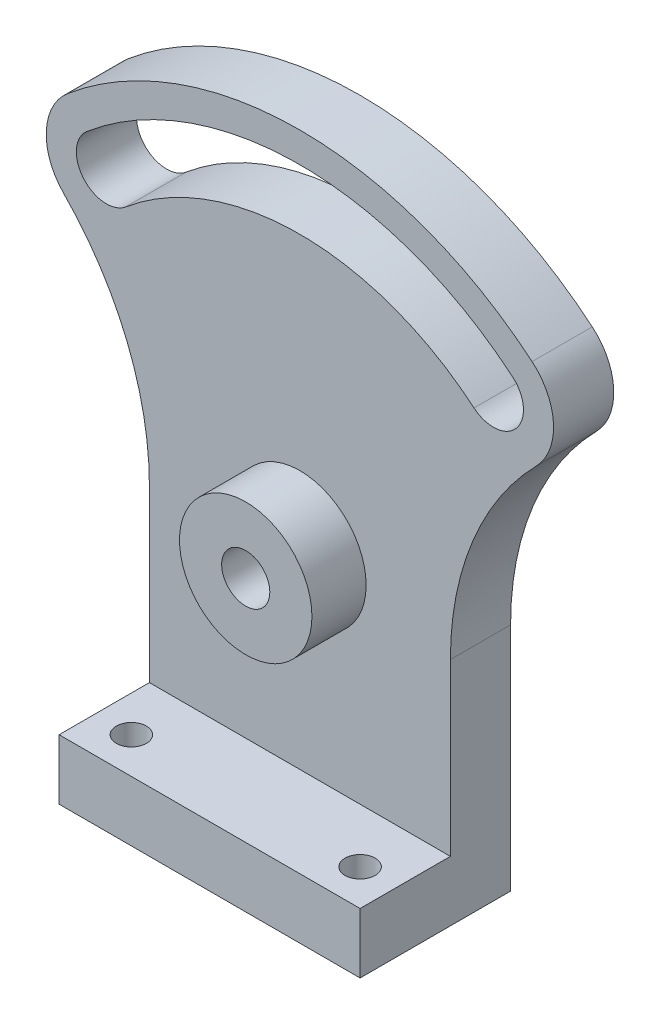
SolidWorks part; units mm, degrees
ref_plane "Front Plane" through (0, 0, 0) normal (0, 0, 1) x (1, 0, 0)
ref_plane "Top Plane" through (0, 0, 0) normal (0, 1, 0) x (1, 0, 0)
ref_plane "Right Plane" through (0, 0, 0) normal (1, 0, 0) x (0, 0, -1)
sketch "Sketch1" plane through (0, 0, 0) normal (0, 0, 1) x (1, 0, 0)
  line L0 (0, 0) -> (0, 23941.5913) construction
  line L1 (0, 0) -> (23941.5913, 0) construction
  line L2 (-25, -11) -> (25, -11)
  line L3 (-25, -21) -> (25, -21)
  line L4 (-25, -21) -> (-25, 17.3145)
  line L6 (25, -21) -> (25, 17.3145)
  circle A0 centre (0, 21) radius 4
  circle A1 centre (0, 21) radius 11
  arc A2 (-32.1394, 59.3022) -> (32.1394, 59.3022) centre (0, 21) cw construction
  arc A3 (38.5673, 66.9627) -> (-38.5673, 66.9627) centre (0, 21) ccw
  arc A4 (25.7115, 51.6418) -> (-25.7115, 51.6418) centre (0, 21) ccw
  arc A5 (25.7115, 51.6418) -> (38.5673, 66.9627) centre (32.1394, 59.3022) ccw
  arc A6 (-38.5673, 66.9627) -> (-25.7115, 51.6418) centre (-32.1394, 59.3022) ccw
  arc A7 (-32.1394, 59.3022) -> (32.1394, 59.3022) centre (0, 21) cw construction
  arc A8 (35.3533, 63.1324) -> (-35.3533, 63.1324) centre (0, 21) ccw
  arc A9 (28.9254, 55.472) -> (-28.9254, 55.472) centre (0, 21) ccw
  arc A10 (28.9254, 55.472) -> (35.3533, 63.1324) centre (32.1394, 59.3022) ccw
  arc A11 (-35.3533, 63.1324) -> (-28.9254, 55.472) centre (-32.1394, 59.3022) ccw
  arc A12 (25, 17.3145) -> (39.2828, 52.3043) centre (75, 17.3145) cw
  arc A13 (-25, 17.3145) -> (-39.2828, 52.3043) centre (-75, 17.3145) ccw
  point P5 (0, 0)
  point P17 (0, 71)
  point P22 (0, 71)
  point P34 (0, 0)
  dimension "D4" = 8
  dimension "D5" = 22
  dimension "D6" = 10
  dimension "D7" = 5
  dimension "D8" = 50
  dimension "D9" = 80
  dimension "D2" = 50
  dimension "D1" = 50
  dimension "D3" = 10
  dimension "D11" = 42
  dimension "D12" = 21
extrude "Boss-Extrude1" add sketch "Sketch1" along normal blind 25 contours L3 L6 L2 L4 region at (0, -16, 0)
extrude "Boss-Extrude2" add sketch "Sketch1<3>" along normal blind 10 contours A13 L4 L2 L6 A12 A5 A4 A6 A1 | A0 | A3 A6 A4 A5 A11 A8 A10 A9 region at (-23.9343, 3.1573, 0) region at (0, 65.0847, 0) region at (0, 21, 0)
sketch "Sketch1<3>" plane through (0, 0, 0) normal (0, 0, 1) x (1, 0, 0) same geometry as "Sketch1"
extrude "Boss-Extrude3" add sketch "Sketch1<4>" along normal blind 19 contours A1 A0 region at (-10.6889, 21, 0)
sketch "Sketch1<4>" plane through (0, 0, 0) normal (0, 0, 1) x (1, 0, 0) same geometry as "Sketch1"
hole_wizard "Ø5.0mm Dowel Hole1" positions "3DSketch1" profile "Sketch2" hole size "Ø5.0" standard "ANSI Metric" end condition up to next
sketch3d "3DSketch1"
  line L0 (-25, -11, 25) -> (-25, -11, 10) construction
  line L1 (-25, -11, 25) -> (25, -11, 25) construction
  line L2 (25, -11, 25) -> (25, -11, 10) construction
  point P0 (-19, -11, 19)
  point P2 (19, -11, 19)
  point P5 (0, 0, 0)
  dimension "D1" = 6
  dimension "D2" = 6
  dimension "D3" = 6
sketch "Sketch2" plane through (-19, -11, 19) normal (1, 0, 0) x (0, 0, 1)
  line L0 (0, 0) -> (0, 10)
  line L1 (0, 10) -> (2.5, 10)
  line L2 (2.5, 10) -> (2.5, 0)
  line L5 (2.5, 0) -> (0, 0)
  line L11 (0, -6.35) -> (0, 107.95) construction
  dimension "Thru Hole Dia." = 5
  dimension "Thru Hole Depth" = 10
